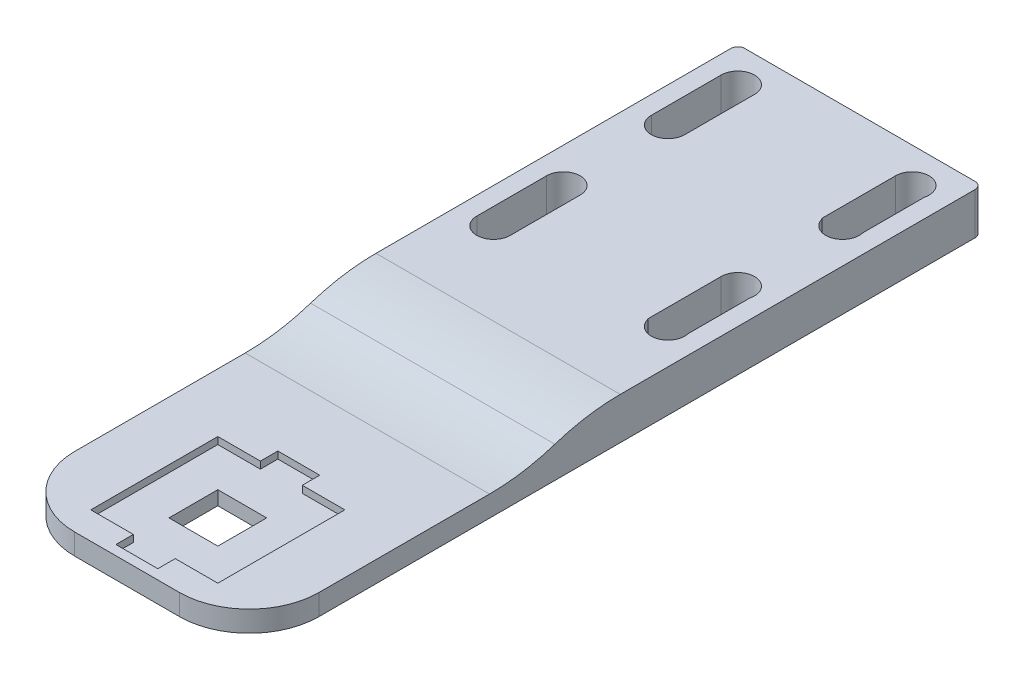
SolidWorks part; units mm, degrees
ref_plane "Front Plane" through (0, 0, 0) normal (0, 0, 1) x (1, 0, 0)
ref_plane "Top Plane" through (0, 0, 0) normal (0, 1, 0) x (1, 0, 0)
ref_plane "Right Plane" through (0, 0, 0) normal (1, 0, 0) x (0, 0, -1)
sketch "Sketch1" plane through (0, 0, 0) normal (0, 1, 0) x (1, 0, 0)
  line L1 (-17.3881, 19.9254) -> (17.6119, 19.9254)
  line L2 (-17.3881, 19.9254) -> (-17.3881, -85.0746)
  line L3 (-17.3881, -85.0746) -> (17.6119, -85.0746)
  line L4 (17.6119, 19.9254) -> (17.6119, -85.0746)
  dimension "D1" = 35
  dimension "D2" = 105
extrude "Boss-Extrude1" add sketch "Sketch1" along normal blind 6
sketch "Sketch2" plane through (0, 6, 0) normal (0, 1, 0) x (1, 0, 0)
  line L0 (17.6119, 19.9254) -> (-17.3881, 19.9254) construction
  line L1 (12.6119, -10.0746) -> (-12.3881, -10.0746)
  line L2 (12.6119, -10.0746) -> (12.6119, 14.9254)
  line L3 (12.6119, 14.9254) -> (-12.3881, 14.9254)
  line L4 (-12.3881, -10.0746) -> (-12.3881, 14.9254)
  line L5 (12.6119, -10.0746) -> (-12.3881, 14.9254) construction
  line L6 (12.6119, 14.9254) -> (-12.3881, -10.0746) construction
  point P0 (0.1119, 2.4254)
  point P7 (0.1119, 19.9254)
  dimension "D1" = 25
  dimension "D2" = 25
  dimension "D3" = 0
  dimension "D4" = 5
hole_wizard "M4 Clearance Hole1" positions "Sketch3" profile "Sketch4" hole size "M4" standard "ANSI Metric" end condition through all
sketch "Sketch3" plane through (0, 6, 0) normal (0, 1, 0) x (1, 0, 0)
  point P0 (-12.3881, 14.9254)
  point P3 (12.6119, 14.9254)
  point P6 (12.6119, -10.0746)
  point P9 (-12.3881, -10.0746)
sketch "Sketch4" plane through (-12.3881, 6, -14.9254) normal (1, 0, 0) x (0, 0, 1)
  line L0 (0, 0) -> (0, 6)
  line L1 (0, 6) -> (2.4, 6)
  line L2 (2.4, 6) -> (2.4, 0)
  line L5 (2.4, 0) -> (0, 0)
  line L11 (0, -6.35) -> (0, 107.95) construction
  dimension "Thru Hole Dia." = 4.8
  dimension "Thru Hole Depth" = 6
pattern_linear "LPattern2" count 2 spacing 10 along (0, 0, 1) of "M4 Clearance Hole1"
sketch "Sketch5" plane through (0, 6, 0) normal (0, 1, 0) x (1, 0, 0)
  line L1 (-14.7881, 14.9254) -> (-9.9881, 14.9254)
  line L2 (-14.7881, 14.9254) -> (-14.7881, 4.9254)
  line L3 (-14.7881, 4.9254) -> (-9.9881, 4.9254)
  line L4 (-9.9881, 14.9254) -> (-9.9881, 4.9254)
  line L5 (-14.7881, -10.0746) -> (-9.9881, -10.0746)
  line L6 (-14.7881, -10.0746) -> (-14.7881, -20.0746)
  line L7 (-14.7881, -20.0746) -> (-9.9881, -20.0746)
  line L8 (-9.9881, -10.0746) -> (-9.9881, -20.0746)
  line L9 (10.2119, 14.9254) -> (14.9426, 14.9254)
  line L10 (10.2119, 14.9254) -> (10.2119, 4.3527)
  line L11 (10.2119, 4.3527) -> (14.9426, 4.3527)
  line L12 (14.9426, 14.9254) -> (14.9426, 4.3527)
  line L13 (10.2119, -10.0746) -> (14.9426, -10.0746)
  line L14 (10.2119, -10.0746) -> (10.2119, -20.6473)
  line L15 (10.2119, -20.6473) -> (14.9426, -20.6473)
  line L16 (14.9426, -10.0746) -> (14.9426, -20.6473)
  circle A0 centre (-12.3881, 14.9254) radius 2.4 construction
  circle A1 centre (-12.3881, 4.9254) radius 2.4 construction
  circle A2 centre (-12.3881, -10.0746) radius 2.4 construction
  circle A3 centre (-12.3881, -20.0746) radius 2.4 construction
  circle A4 centre (12.6119, 14.9254) radius 2.4 construction
  circle A5 centre (12.6119, 4.9254) radius 2.4 construction
  circle A6 centre (12.6119, -10.0746) radius 2.4 construction
  circle A7 centre (12.6119, -20.0746) radius 2.4 construction
extrude "Cut-Extrude1" cut sketch "Sketch5" against normal through all
sketch "Sketch6" plane through (0, 6, 0) normal (0, 1, 0) x (1, 0, 0)
  line L1 (9.2119, -81.1746) -> (-8.9881, -81.1746)
  line L2 (9.2119, -81.1746) -> (9.2119, -62.9746)
  line L3 (9.2119, -62.9746) -> (-8.9881, -62.9746)
  line L4 (-8.9881, -81.1746) -> (-8.9881, -62.9746)
  line L5 (9.2119, -81.1746) -> (-8.9881, -62.9746) construction
  line L6 (9.2119, -62.9746) -> (-8.9881, -81.1746) construction
  line L9 (-17.3881, -85.0746) -> (17.6119, -85.0746) construction
  point P0 (0.1119, -72.0746)
  point P7 (0.1119, -85.0746)
  dimension "D1" = 18.2
  dimension "D2" = 18.2
  dimension "D3" = 13
  dimension "D4" = 0
extrude "Cut-Extrude2" cut sketch "Sketch6" against normal offset from surface (4 mm away) 2 up to face at (-12.3881, 0, 15.0746)
sketch "Sketch7" plane through (0, 2, 0) normal (0, 1, 0) x (1, 0, 0)
  line L0 (9.2119, -81.1746) -> (9.2119, -62.9746) construction
  line L1 (3.6119, -75.5746) -> (-3.3881, -75.5746)
  line L2 (3.6119, -75.5746) -> (3.6119, -68.5746)
  line L3 (3.6119, -68.5746) -> (-3.3881, -68.5746)
  line L4 (-3.3881, -75.5746) -> (-3.3881, -68.5746)
  line L5 (3.6119, -75.5746) -> (-3.3881, -68.5746) construction
  line L6 (3.6119, -68.5746) -> (-3.3881, -75.5746) construction
  line L7 (-17.3881, -85.0746) -> (17.6119, -85.0746) construction
  point P0 (0.1119, -72.0746)
  point P7 (9.2119, -72.0746)
  point P10 (0.1119, -85.0746)
  dimension "D1" = 0
  dimension "D2" = 0
  dimension "D3" = 7
  dimension "D4" = 7
extrude "Cut-Extrude3" cut sketch "Sketch7" against normal through all
sketch "Sketch8" plane through (0, 6, 0) normal (0, 1, 0) x (1, 0, 0)
  line L0 (9.2119, -62.9746) -> (-8.9881, -62.9746) construction
  line L1 (3.1119, -83.6746) -> (-2.8881, -83.6746)
  line L2 (3.1119, -83.6746) -> (3.1119, -60.4746)
  line L3 (3.1119, -60.4746) -> (-2.8881, -60.4746)
  line L4 (-2.8881, -83.6746) -> (-2.8881, -60.4746)
  line L5 (3.1119, -83.6746) -> (-2.8881, -60.4746) construction
  line L6 (3.1119, -60.4746) -> (-2.8881, -83.6746) construction
  line L7 (9.2119, -81.1746) -> (-8.9881, -81.1746) construction
  line L9 (3.6119, -68.5746) -> (-3.3881, -68.5746) construction
  point P0 (0.1119, -72.0746)
  point P11 (0.1119, -68.5746)
  dimension "D1" = 2.5
  dimension "D2" = 2.5
  dimension "D3" = 6
  dimension "D4" = 0
extrude "Cut-Extrude4" cut sketch "Sketch8" against normal up to surface (4 mm away) up to face at (0.1119, 2, 72.0746)
fillet "Fillet1" radius 10 2 edges at (17.6119, 3, 85.0746) (-17.3881, 3, 85.0746)
sketch "Sketch9" plane through (0, 0, 0) normal (0, -1, 0) x (1, 0, 0)
  line L0 (-17.3881, -19.9254) -> (-17.3881, 75.0746) construction
  line L1 (-17.3881, 37.5746) -> (19.6619, 37.5746)
  line L2 (-17.3881, 37.5746) -> (-17.3881, 85.0746)
  line L3 (-17.3881, 85.0746) -> (19.6619, 85.0746)
  line L4 (19.6619, 37.5746) -> (19.6619, 85.0746)
  line L5 (-7.3881, 85.0746) -> (7.6119, 85.0746) construction
  line L6 (9.2119, 62.9746) -> (3.1119, 62.9746) construction
  dimension "D1" = 25.4
  dimension "D2" = 0
extrude "Cut-Extrude5" cut sketch "Sketch9" along normal offset from surface (3 mm away) 3 from surface up to face at (0.1119, 0, 72.0746) starting at face at (0.1119, 6, 72.0746)
fillet "Fillet2" radius 30 1 edges at (0.1119, 3, 37.5746)
fillet "Fillet3" radius 30 1 edges at (0.1119, 6, 37.5746)
fillet "Fillet4" radius 1 2 edges at (17.6119, 3, -19.9254) (-17.3881, 3, -19.9254)
ref_plane "Plane11" through (3.1119, 3, 83.6746) normal (-1, 0, 0) x (0, 0, 1)
sketch "Sketch14" plane through (-3.3881, 0, 0) normal (1, 0, 0) x (0, 0, -1)
  line L1 (-68.5746, 0) -> (-75.5746, 0)
  line L2 (-68.5746, 0) -> (-68.5746, 2)
  line L3 (-68.5746, 2) -> (-75.5746, 2)
  line L4 (-75.5746, 0) -> (-75.5746, 2)
extrude "Boss-Extrude2" add sketch "Sketch14" along normal up to surface (7 mm away) contours L2 L1 L4 L3 up to face at (3.6119, 1, 72.0746)
sketch "Sketch16" plane through (0, 3, 0) normal (0, 1, 0) x (1, 0, 0)
  line L0 (-17.3881, -75.0746) -> (17.6119, -75.0746)
  line L1 (-17.3881, -75.0746) -> (-17.3881, -50.6513) construction
  line L2 (17.6119, -75.0746) -> (17.6119, -50.6513) construction
  line L3 (0.1119, -75.0746) -> (0.1119, -85.0746)
  line L4 (-3.3881, -78.5746) -> (3.6119, -78.5746)
  line L5 (-3.3881, -78.5746) -> (-3.3881, -71.5746)
  line L6 (-3.3881, -71.5746) -> (3.6119, -71.5746)
  line L7 (3.6119, -78.5746) -> (3.6119, -71.5746)
  line L8 (-3.3881, -78.5746) -> (3.6119, -71.5746) construction
  line L9 (-3.3881, -71.5746) -> (3.6119, -78.5746) construction
  line L10 (7.6119, -85.0746) -> (-7.3881, -85.0746) construction
  point P6 (0.1119, -75.0746)
sketch "Sketch17" plane through (0, 2, 0) normal (0, 1, 0) x (1, 0, 0)
  line L0 (-8.9881, -62.9746) -> (9.2119, -81.1746)
  line L1 (9.2119, -62.9746) -> (-8.9881, -81.1746)
  line L3 (-3.3881, -75.5746) -> (3.6119, -75.5746)
  line L4 (-3.3881, -75.5746) -> (-3.3881, -68.5746)
  line L5 (-3.3881, -68.5746) -> (3.6119, -68.5746)
  line L6 (3.6119, -75.5746) -> (3.6119, -68.5746)
  line L7 (-3.3881, -75.5746) -> (3.6119, -68.5746) construction
  line L8 (-3.3881, -68.5746) -> (3.6119, -75.5746) construction
  point P8 (0.1119, -72.0746)
extrude "Cut-Extrude6" cut sketch "Sketch17" against normal blind 10 contours L4 L3 L6 L5
